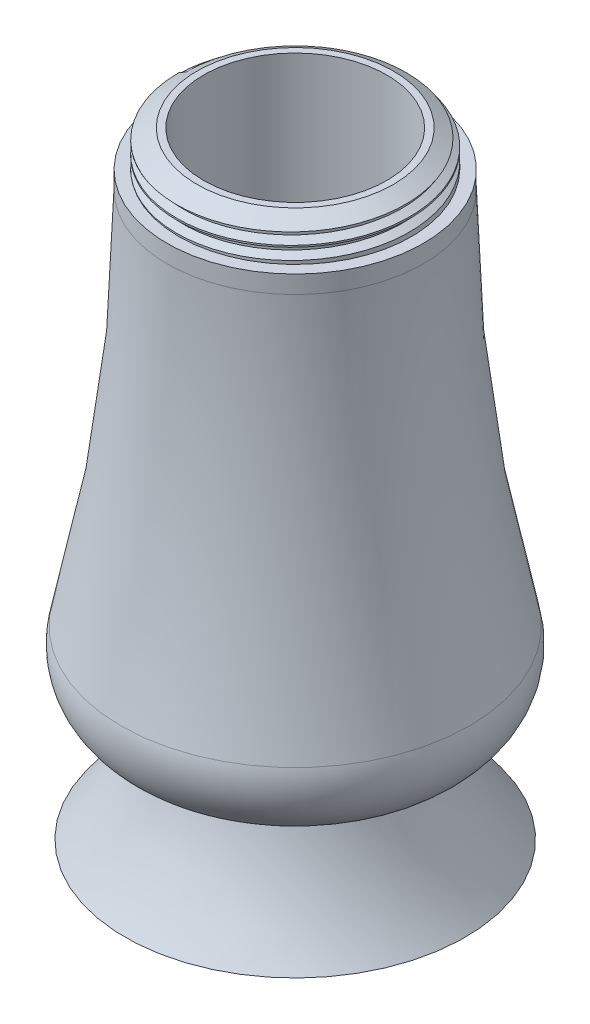
SolidWorks part; units mm, degrees
ref_plane "Front Plane" through (0, 0, 0) normal (0, 0, 1) x (1, 0, 0)
ref_plane "Top Plane" through (0, 0, 0) normal (0, 1, 0) x (1, 0, 0)
ref_plane "Right Plane" through (0, 0, 0) normal (1, 0, 0) x (0, 0, -1)
sketch "Szkic1" plane through (0, 0, 0) normal (0, 1, 0) x (1, 0, 0)
  circle A0 centre (0, 0) radius 13
  dimension "D1" = 26
sketch "Szkic2" plane through (0, 0, 0) normal (0, 0, 1) x (1, 0, 0)
  line L0 (0, 0) -> (0, 8)
  line L1 (13, 0) -> (-13, 0) construction
  line L3 (13, 0) -> (0, 0)
  line L4 (9.0274, 8) -> (0, 8)
  arc A1 (13, 0) -> (9.0274, 8) centre (28.8569, 12.8606) cw
  dimension "D1" = 8
revolve "Obrót1" add sketch "Szkic2" angle 360 about L0
sketch "Szkic3" plane through (0, 8, 0) normal (0, 1, 0) x (1, 0, 0)
  circle A0 centre (0, 0) radius 15
  dimension "D1" = 30
sketch "Szkic4" plane through (0, 0, 0) normal (0, 0, 1) x (1, 0, 0)
  line L0 (0, 8) -> (0, 43)
  line L1 (15, 8) -> (-15, 8) construction
  line L3 (15, 8) -> (0, 8)
  line L5 (8.9, 47.1223) -> (0, 47.1223)
  line L6 (0, 47.1223) -> (0, 43)
  line L12 (8.9, 45.0612) -> (8.9, 47.1223)
  line L13 (8.9, 45.0612) -> (8.9, 44.5978)
  line L16 (8.9, 44.5978) -> (8.9, 44.463)
  line L19 (8.9, 44.463) -> (8.9, 44.3591)
  line L20 (8.9, 44.3591) -> (9.8, 44.3591)
  line L21 (9.8, 44.3591) -> (9.8, 43)
  arc A1 (9.8, 43) -> (15, 8) centre (132.3156, 43.316) ccw
  dimension "D1" = 35
  dimension "D2" = 9.8
  dimension "D3" = 15
  dimension "D4" = 8.9
revolve "Obrót2" add sketch "Szkic4" angle 360 about L0
thread "Gwint1" pitch 1 method cut profile "Profil gwintu1" start angle 0, offset 0, length 2, pitch 1, diameter 17.8
ref_plane "Płaszczyzna1" through (-8.9, 47.1223, 0) normal (0, 0, 1) x (-1, 0, 0)
sketch "Profil gwintu1" plane through (-8.9, 47.1223, 0) normal (0, 0, 1) x (-1, 0, 0)
  line L0 (0, 0) -> (0, 1) construction
  line L11 (0, 0) -> (0, 0.875)
  line L12 (0, 0.875) -> (-0.5413, 0.5625)
  line L13 (-0.5413, 0.5625) -> (-0.5413, 0.3125)
  line L15 (-0.5413, 0.3125) -> (0, 0)
  line L17 (-0.5413, 0.4375) -> (0, 0.4375) construction
  point P2 (0, 0)
  dimension "Pitch" = 1
  dimension "Profile_Angle" = 60
  dimension "Profile_Land" = 0.25
  dimension "Profile_Height" = 0.5413
sketch "Szkic8" plane through (0, 47.1223, 0) normal (0, 1, 0) x (1, 0, 0)
  circle A0 centre (0, 0) radius 13
sketch "Szkic9" plane through (0, 0, 0) normal (0, 0, 1) x (1, 0, 0)
  line L5 (8.9, 47.1223) -> (8.9, 46.3223)
  line L6 (8.9, 46.3223) -> (7.5144, 47.1223)
  line L7 (13, 47.1223) -> (-13, 47.1223) construction
  line L8 (7.5144, 47.1223) -> (8.9, 47.1223)
  dimension "D1" = 60
  dimension "D2" = 0.8
sweep "Wycięcie-wyciągnięcie po ścieżce1" cut profiles "Szkic9" path "Szkic8"
sketch "Szkic10" plane through (0, 47.1223, 0) normal (0, 1, 0) x (1, 0, 0)
  circle A0 centre (0, 0) radius 7
  dimension "D1" = 14
extrude "Wytnij-wyciągnięcie2" cut sketch "Szkic10" against normal blind 25
fillet "Zaokrąglenie1" radius 5 1 edges at (0, 8, -15)
